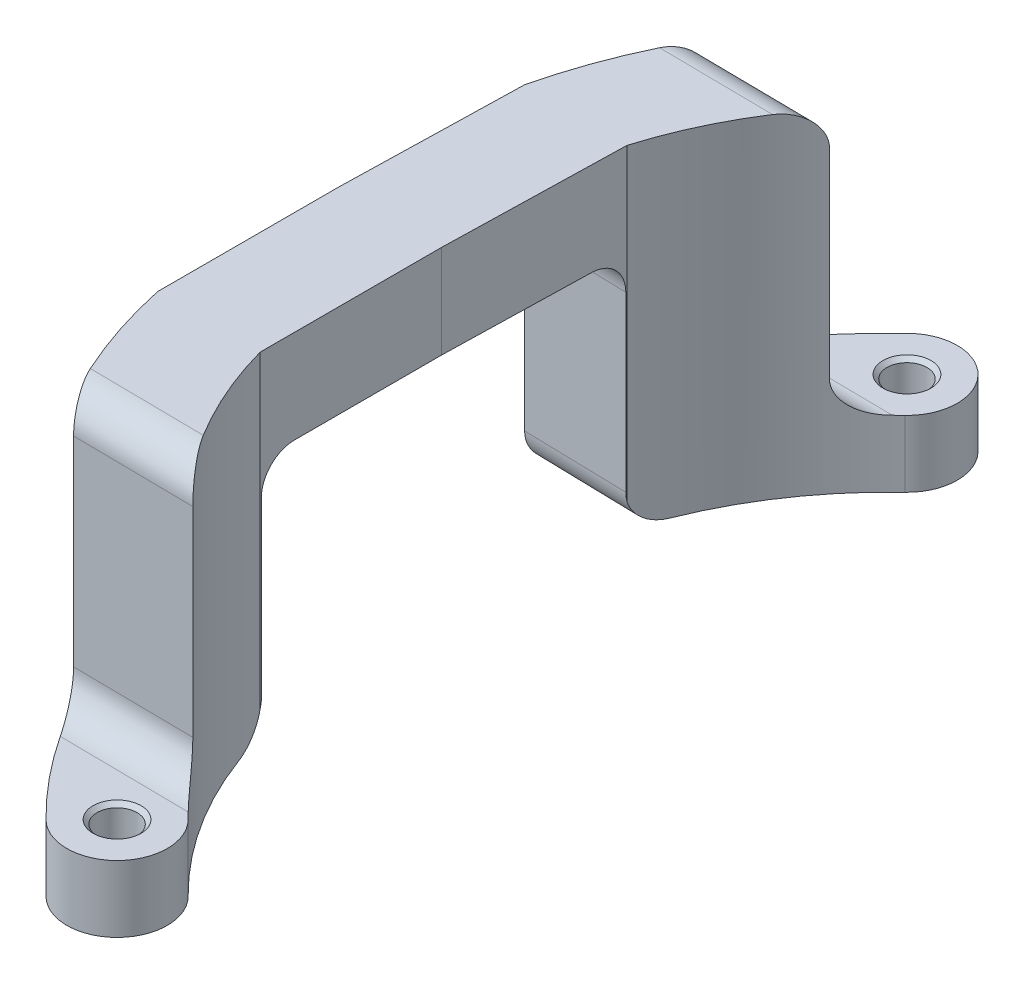
SolidWorks part; units mm, degrees
other "Soporte Cámara - Conector"
ref_plane "Alzado" through (0, 0, 0) normal (0, 0, 1) x (1, 0, 0)
ref_plane "Planta" through (0, 0, 0) normal (0, 1, 0) x (1, 0, 0)
ref_plane "Vista lateral" through (0, 0, 0) normal (1, 0, 0) x (0, 0, -1)
sketch "Croquis2" plane through (0, 0, 0) normal (0, 1, 0) x (1, 0, 0)
  line L0 (-4.6145, 2.228) -> (4.4391, 2.1185)
  line L2 (-8.3489, 12.2739) -> (-0.5669, 12.1798)
  arc A0 (1.7899, -6.2471) -> (7.0871, -0.8787) centre (4.4385, -3.5629) ccw
  arc A1 (-8.3489, 12.2739) -> (1.7899, -6.2471) centre (27.6163, 19.9264) ccw
  arc A2 (-0.5669, 12.1798) -> (7.0871, -0.8787) centre (27.6163, 19.9264) ccw
  circle A4 centre (4.4385, -3.5629) radius 1.5
  dimension "D1" = 10
extrude "Saliente-Extruir1" add sketch "Croquis2" along normal blind 5 contours A2 L0 A1 A0 region at (2.4719, 0, 1.8984)
extrude "Saliente-Extruir2" add sketch "Croquis2<3>" along normal blind 25 contours A2 A1 L0 region at (-2.5626, 0, -7.0787)
sketch "Croquis2<3>" plane through (0, 0, 0) normal (0, 1, 0) x (1, 0, 0) same geometry as "Croquis2"
hole_wizard "Avellanado para tornillo con cabeza plana avellanada de M1.61" positions "Croquis4" profile "Croquis5" countersink size "M1.6" standard "ISO" end condition through all
sketch "Croquis4" plane through (0, 5, 0) normal (0, 1, 0) x (1, 0, 0)
  point P0 (4.4385, -3.5629)
sketch "Croquis5" plane through (4.4385, 5, 3.5629) normal (1, 0, 0) x (0, 0, 1)
  line L0 (0, 0) -> (0, 5)
  line L1 (0, 5) -> (0.9, 5)
  line L2 (0.9, 5) -> (0.9, 0.9)
  line L3 (0.9, 0.9) -> (1.8, 0)
  line L5 (1.8, 0) -> (0, 0)
  line L6 (-0.9, 0.9) -> (-1.8, 0) construction
  line L11 (0, -6.35) -> (0, 107.95) construction
  dimension "Diámetro de taladro hasta el siguiente" = 1.8
  dimension "Profundidad de taladro hasta el siguiente" = 5
  dimension "Diámetro de avellanado cercano" = 3.6
  dimension "Ángulo de avellanado cercano" = 90
sketch "Croquis8" plane through (0, 0, 0) normal (0, 1, 0) x (1, 0, 0)
  line L0 (-4.4579, 12.2269) -> (-4.4579, 42.2269) construction
  line L1 (-8.3489, 12.2739) -> (-0.5669, 12.1798) construction
  line L3 (-8.3489, 42.1798) -> (-0.5669, 42.0857)
  line L4 (-8.3489, 42.1798) -> (-8.3489, 12.2739)
  line L5 (-8.3489, 12.2739) -> (-0.5669, 12.1798)
  line L6 (-0.5669, 42.0857) -> (-0.5669, 12.1798)
  point P4 (-4.4579, 27.2269)
extrude "Saliente-Extruir3" add sketch "Croquis8" along normal blind 25
sketch "Croquis13" plane through (-8.3489, 0, 0) normal (-1, 0, 0) x (0, 0, 1)
  line L7 (-12.2739, 25) -> (-12.2739, 0) construction
  line L8 (-42.1798, 18) -> (-12.2739, 18)
  line L9 (-42.1798, 18) -> (-42.1798, 0)
  line L10 (-42.1798, 0) -> (-12.2739, 0)
  line L11 (-12.2739, 18) -> (-12.2739, 0)
  line L12 (-42.1798, 18) -> (-12.2739, 0) construction
  line L13 (-42.1798, 0) -> (-12.2739, 18) construction
  line L14 (-42.1798, 0) -> (-12.2739, 0) construction
  point P0 (-27.2269, 9)
  dimension "D1" = 18
extrude "Cortar-Extruir3" cut sketch "Croquis13" against normal up to next
sketch "Croquis42" plane through (0.5089, 0, -42.0727) normal (0.0121, 0, -0.9999) x (-0.9999, 0, -0.0121)
  line L0 (1.0759, 25) -> (1.0759, 18)
  line L1 (1.0759, 18) -> (8.8585, 18)
extrude "Cortar-Extruir7" cut sketch "Croquis42" against normal blind 16.3 and the other way through all
sketch "Croquis44" plane through (-1.0759, 0, -0.013) normal (-0.9999, 0, -0.0121) x (-0.0121, 0, 0.9999)
  line L1 (-42.0757, 25) -> (-25.7757, 25)
  line L2 (-42.0757, 25) -> (-42.0757, 18)
  line L3 (-42.0757, 18) -> (-25.7757, 18)
  line L4 (-25.7757, 25) -> (-25.7757, 18)
  line L5 (-42.0757, 25) -> (-25.7757, 18) construction
  line L6 (-42.0757, 18) -> (-25.7757, 25) construction
  point P0 (-33.9257, 21.5)
extrude "Cortar-Extruir8" cut sketch "Croquis44" against normal blind 1
fillet "Redondeo1" radius 2.5 4 edges at (-4.4579, 0, -12.2739) (-4.4579, 18, -12.2739) (-0.0877, 25, -2.1733) (-0.0877, 5, -2.1733)
mirror "Simetría1" about plane through (-8.5461, 25, -25.881) normal (-0.0121, 0, 0.9999) of bodies 118
